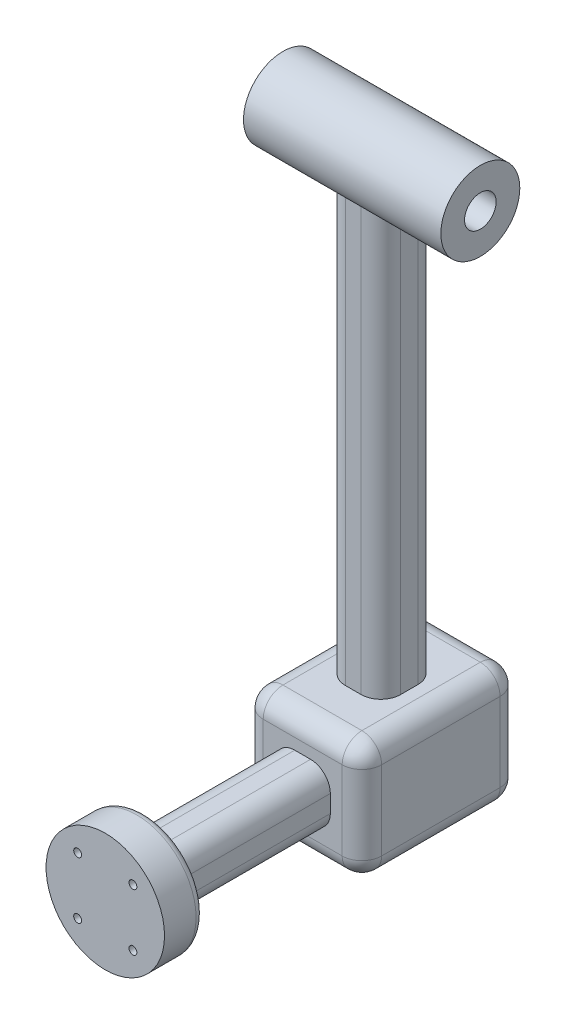
SolidWorks part; units mm, degrees
material "1060 Alloy"
ref_plane "Front Plane" through (0, 0, 0) normal (0, 0, 1) x (1, 0, 0)
ref_plane "Top Plane" through (0, 0, 0) normal (0, 1, 0) x (1, 0, 0)
ref_plane "Right Plane" through (0, 0, 0) normal (1, 0, 0) x (0, 0, -1)
sketch "Sketch1" plane through (0, 0, 0) normal (0, 0, 1) x (1, 0, 0)
  line L1 (-19.05, -19.05) -> (19.05, -19.05)
  line L2 (-19.05, -19.05) -> (-19.05, 19.05)
  line L3 (-19.05, 19.05) -> (19.05, 19.05)
  line L4 (19.05, -19.05) -> (19.05, 19.05)
  line L5 (-19.05, -19.05) -> (19.05, 19.05) construction
  line L6 (-19.05, 19.05) -> (19.05, -19.05) construction
  point P0 (0, 0)
  dimension "D1" = 38.1
  dimension "D2" = 38.1
extrude "Boss-Extrude1" add sketch "Sketch1" along normal blind 50.8 contours L4 L3 L2 L1
sketch "Sketch2" plane through (0, 0, 50.8) normal (0, 0, 1) x (1, 0, 0)
  line L1 (-8.89, -9.144) -> (8.89, -9.144)
  line L2 (-8.89, -9.144) -> (-8.89, 9.144)
  line L3 (-8.89, 9.144) -> (8.89, 9.144)
  line L4 (8.89, -9.144) -> (8.89, 9.144)
  line L5 (-8.89, -9.144) -> (8.89, 9.144) construction
  line L6 (-8.89, 9.144) -> (8.89, -9.144) construction
  point P0 (0, 0)
  dimension "D1" = 18.288
  dimension "D2" = 17.78
extrude "Boss-Extrude2" add sketch "Sketch2" along normal blind 50.8 contours L4 L3 L2 L1
sketch "Sketch3" plane through (0, 0, 101.6) normal (0, 0, 1) x (1, 0, 0)
  circle A0 centre (0, 0) radius 19.05
  dimension "D1" = 38.1
extrude "Boss-Extrude3" add sketch "Sketch3" along normal blind 12.7 contours A0
sketch "Sketch4" plane through (0, 19.05, 0) normal (0, 1, 0) x (1, 0, 0)
  line L1 (-8.89, -34.544) -> (8.89, -34.544)
  line L2 (-8.89, -34.544) -> (-8.89, -16.256)
  line L3 (-8.89, -16.256) -> (8.89, -16.256)
  line L4 (8.89, -34.544) -> (8.89, -16.256)
  line L5 (-8.89, -34.544) -> (8.89, -16.256) construction
  line L6 (-8.89, -16.256) -> (8.89, -34.544) construction
  line L8 (19.05, -50.8) -> (19.05, 0) construction
  point P0 (0, -25.4)
  point P13 (19.05, -25.4)
  dimension "D1" = 18.288
  dimension "D2" = 17.78
extrude "Boss-Extrude4" add sketch "Sketch4" along normal blind 137.16 contours L4 L3 L2 L1
sketch "Sketch6" plane through (0, 0, 0) normal (1, 0, 0) x (0, 0, -1)
  line L0 (-34.544, 156.21) -> (-16.256, 156.21) construction
  circle A0 centre (-25.4, 163.83) radius 12.7
  point P5 (-25.4, 156.21)
  dimension "D1" = 25.4
  dimension "D2" = 7.62
extrude "Boss-Extrude5" add sketch "Sketch6" along normal mid plane 63.5 contours A0
sketch "Sketch7" plane through (31.75, 0, 0) normal (1, 0, 0) x (0, 0, -1)
  circle A0 centre (-25.4, 163.83) radius 5.08
  dimension "D1" = 10.16
extrude "Cut-Extrude1" cut sketch "Sketch7" against normal blind 63.5 contours A0
sketch "Sketch8" plane through (0, 0, 114.3) normal (0, 0, 1) x (1, 0, 0)
  line L1 (8.89, -9.144) -> (-8.89, -9.144)
  line L2 (8.89, -9.144) -> (8.89, 9.144)
  line L3 (8.89, 9.144) -> (-8.89, 9.144)
  line L4 (-8.89, -9.144) -> (-8.89, 9.144)
  line L5 (8.89, -9.144) -> (-8.89, 9.144) construction
  line L6 (8.89, 9.144) -> (-8.89, -9.144) construction
  circle A0 centre (8.89, 9.144) radius 1.27
  circle A1 centre (-8.89, 9.144) radius 1.27
  circle A2 centre (8.89, -9.144) radius 1.27
  circle A3 centre (-8.89, -9.144) radius 1.27
  point P0 (0, 0)
  dimension "D3" = 2.54
  dimension "D4" = 2.54
  dimension "D5" = 2.54
  dimension "D6" = 2.54
  dimension "D1" = 18.288
  dimension "D2" = 17.78
extrude "Cut-Extrude2" cut sketch "Sketch8" against normal blind 10.16 contours A0
extrude "Cut-Extrude3" cut sketch "Sketch8<3>" against normal blind 10.16 contours A2
sketch "Sketch8<3>" plane through (0, 0, 114.3) normal (0, 0, 1) x (1, 0, 0) same geometry as "Sketch8"
extrude "Cut-Extrude4" cut sketch "Sketch8<4>" against normal blind 10.16 contours A3
sketch "Sketch8<4>" plane through (0, 0, 114.3) normal (0, 0, 1) x (1, 0, 0) same geometry as "Sketch8"
extrude "Cut-Extrude5" cut sketch "Sketch8<5>" against normal blind 10.16 contours A1
sketch "Sketch8<5>" plane through (0, 0, 114.3) normal (0, 0, 1) x (1, 0, 0) same geometry as "Sketch8"
fillet "Fillet1" radius 6.35 20 edges at (-19.05, 19.05, 25.4) (-19.05, 0, 50.8) (-19.05, -19.05, 25.4) (-19.05, 0, 0) (8.89, -9.144, 76.2) (8.89, 9.144, 76.2) (-8.89, -9.144, 76.2) (0, 19.05, 50.8) (-8.89, 9.144, 76.2) (0, -19.05, 0) (0, 19.05, 0) (19.05, 19.05, 25.4) (19.05, 0, 0) (19.05, -19.05, 25.4) (0, -19.05, 50.8) (19.05, 0, 50.8) (-8.89, 87.0333, 34.544) (-8.89, 87.0333, 16.256) (8.89, 87.0333, 16.256) (8.89, 87.0333, 34.544)
sketch "Sketch10" plane through (0, 0, 104.14) normal (0, 0, 1) x (1, 0, 0)
  circle A0 centre (-8.89, -9.144) radius 1.905
  dimension "D1" = 3.81
extrude "Cut-Extrude6" cut sketch "Sketch10" against normal blind 2.54
mirror "Mirror1" about plane through (0, 0, 0) normal (0, 1, 0) of "Cut-Extrude6"
mirror "Mirror2" about plane through (0, 0, 0) normal (1, 0, 0) of "Mirror1"
fillet "Fillet2" radius 2.54 1 edges at (19.05, 0, 101.6)
